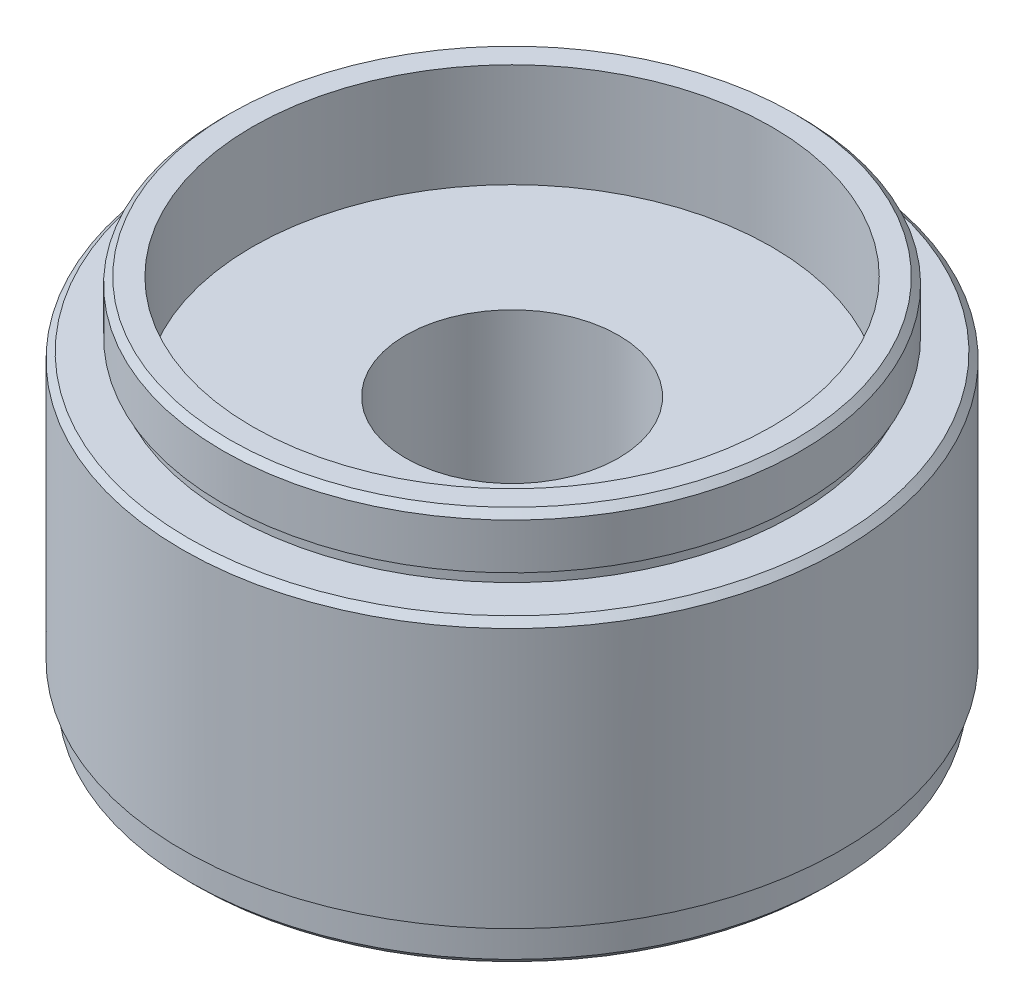
SolidWorks part; units mm, degrees
ref_plane "Front Plane" through (0, 0, 0) normal (0, 0, 1) x (1, 0, 0)
ref_plane "Top Plane" through (0, 0, 0) normal (0, 1, 0) x (1, 0, 0)
ref_plane "Right Plane" through (0, 0, 0) normal (1, 0, 0) x (0, 0, -1)
sketch "Sketch1" plane through (0, 0, 0) normal (0, 1, 0) x (1, 0, 0)
  circle A0 centre (0, 0) radius 25.385
extrude "Boss-Extrude1" add sketch "Sketch1" along normal blind 28.54 separate body
sketch "Sketch2" plane through (0, 0, 0) normal (0, -1, 0) x (1, 0, 0)
  circle A0 centre (0, 0) radius 24.75
extrude "Cut-Extrude1" cut sketch "Sketch2" against normal blind 3 flip side to cut
sketch "Sketch3" plane through (0, 28.54, 0) normal (0, 1, 0) x (1, 0, 0)
  circle A0 centre (0, 0) radius 22.25
extrude "Cut-Extrude2" cut sketch "Sketch3" against normal blind 5.02 flip side to cut
sketch "Sketch4" plane through (0, 23.52, 0) normal (0, 1, 0) x (1, 0, 0)
  circle A0 centre (0, 0) radius 21.75
extrude "Cut-Extrude3" cut sketch "Sketch4" along normal blind 1 flip side to cut
sketch "Sketch5" plane through (0, 28.54, 0) normal (0, 1, 0) x (1, 0, 0)
  circle A0 centre (0, 0) radius 20
extrude "Cut-Extrude4" cut sketch "Sketch5" against normal blind 8
sketch "Sketch6" plane through (0, 0, 0) normal (0, -1, 0) x (1, 0, 0)
  circle A0 centre (0, 0) radius 8.2
extrude "Cut-Extrude5" cut sketch "Sketch6" against normal through all
sketch "Sketch7" plane through (0, 0, 0) normal (0, -1, 0) x (1, 0, 0)
  circle A0 centre (0, 0) radius 13.5
extrude "Cut-Extrude6" cut sketch "Sketch7" against normal blind 5
chamfer "Chamfer1" distance 0.5 angle 45 1 edges at (0, 0, -24.75) first distance on face at (0, 0, -13.5)
chamfer "Chamfer2" distance 0.5 angle 45 1 edges at (0, 28.54, 22.25) first distance on face at (0, 28.54, 20)
chamfer "Chamfer3" distance 0.5 angle 45 1 edges at (0, 23.52, 25.385) first distance on face at (0, 23.52, 25.385)
